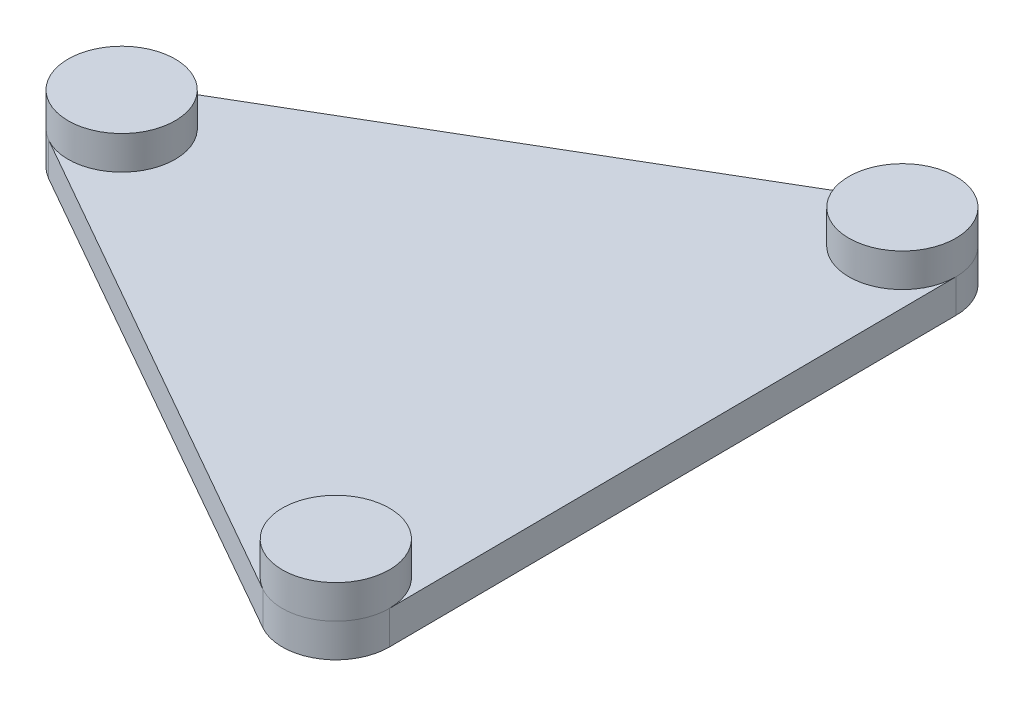
SolidWorks part; units mm, degrees
ref_plane "Front Plane" through (0, 0, 0) normal (0, 0, 1) x (1, 0, 0)
ref_plane "Top Plane" through (0, 0, 0) normal (0, 1, 0) x (1, 0, 0)
ref_plane "Right Plane" through (0, 0, 0) normal (1, 0, 0) x (0, 0, -1)
sketch "Sketch1" plane through (0, 0, 0) normal (0, 1, 0) x (1, 0, 0)
  line L1 (40.933, 72.0384) -> (-82.8536, -0.5702)
  line L2 (-82.8536, -0.5702) -> (41.9206, -71.4682)
  line L3 (41.9206, -71.4682) -> (40.933, 72.0384)
  circle A0 centre (0, 0) radius 41.4278 construction
  dimension "D1" = 143.51
extrude "Boss-Extrude1" add sketch "Sketch1" along normal blind 6.35
sketch "Sketch2" plane through (0, 6.35, 0) normal (0, 1, 0) x (1, 0, 0)
  line L0 (0, 0) -> (-82.8536, -0.5702) construction
  line L1 (40.933, 72.0384) -> (-82.8536, -0.5702) construction
  circle A0 centre (-62.5341, -0.4303) radius 10.16
  circle A3 centre (30.8944, 54.3712) radius 10.16
  circle A4 centre (31.6397, -53.9409) radius 10.16
  dimension "D1" = 20.32
  dimension "D2" = 3
extrude "Boss-Extrude2" add sketch "Sketch2" along normal blind 6.35
fillet "Fillet1" radius 10.16 3 edges at (40.933, 3.175, -72.0384) (41.9206, 3.175, 71.4682) (-82.8536, 3.175, 0.5702)
